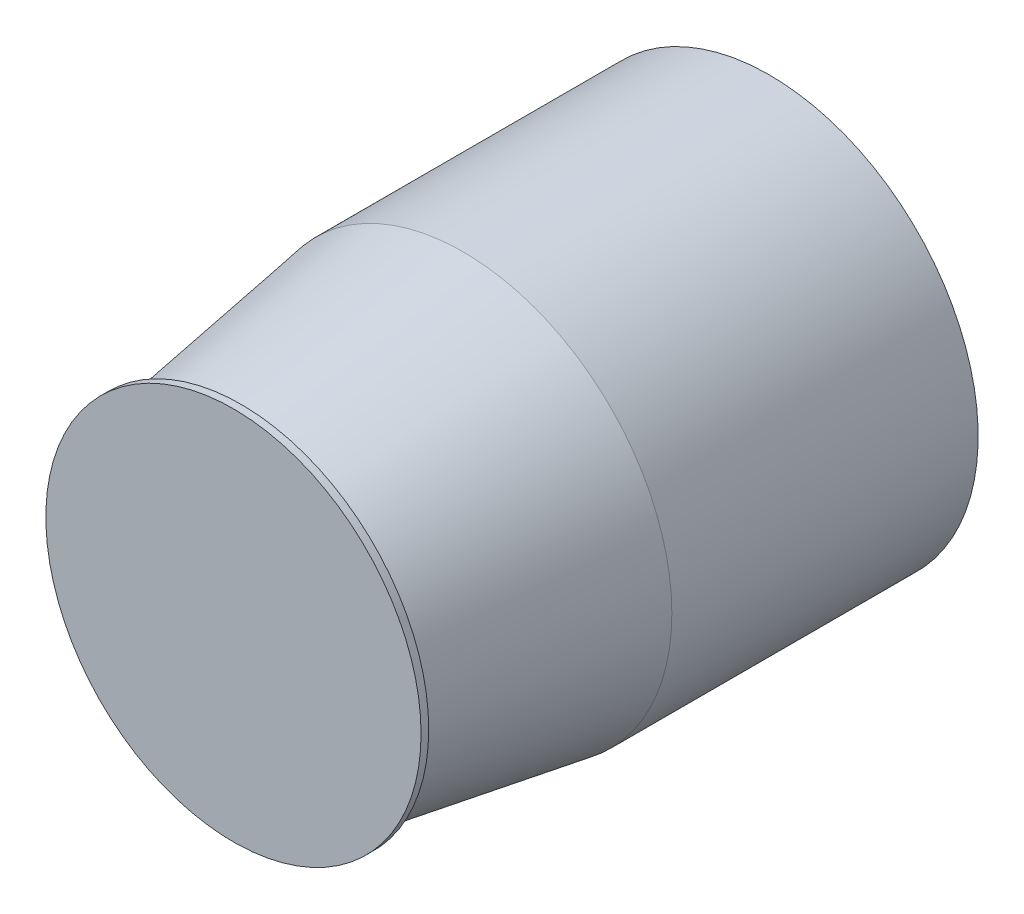
SolidWorks part; units mm, degrees
ref_plane "Front Plane" through (0, 0, 0) normal (0, 0, 1) x (1, 0, 0)
ref_plane "Top Plane" through (0, 0, 0) normal (0, 1, 0) x (1, 0, 0)
ref_plane "Right Plane" through (0, 0, 0) normal (1, 0, 0) x (0, 0, -1)
sketch "Sketch1" plane through (0, 0, 0) normal (0, 0, 1) x (1, 0, 0)
  circle A0 centre (0, 0) radius 11.25
  circle A1 centre (0, 0) radius 12.25
  dimension "D1" = 22.5
  dimension "D2" = 1
extrude "Boss-Extrude1" add sketch "Sketch1" against normal blind 15 draft 9 contours A0 region at (0, 0, 0) draft outward yes
extrude "Boss-Extrude2" add sketch "Sketch1<3>" against normal blind 0.5 contours A1
sketch "Sketch1<3>" plane through (0, 0, 0) normal (0, 0, 1) x (1, 0, 0) same geometry as "Sketch1"
sketch "Sketch2" plane through (0, 0, -15) normal (0, 0, -1) x (-1, 0, 0)
  circle A1 centre (0, 0) radius 13.6258
  circle A2 centre (0, 0) radius 13.6258
  dimension "D1" = 0
extrude "Boss-Extrude3" add sketch "Sketch2" along normal blind 20
